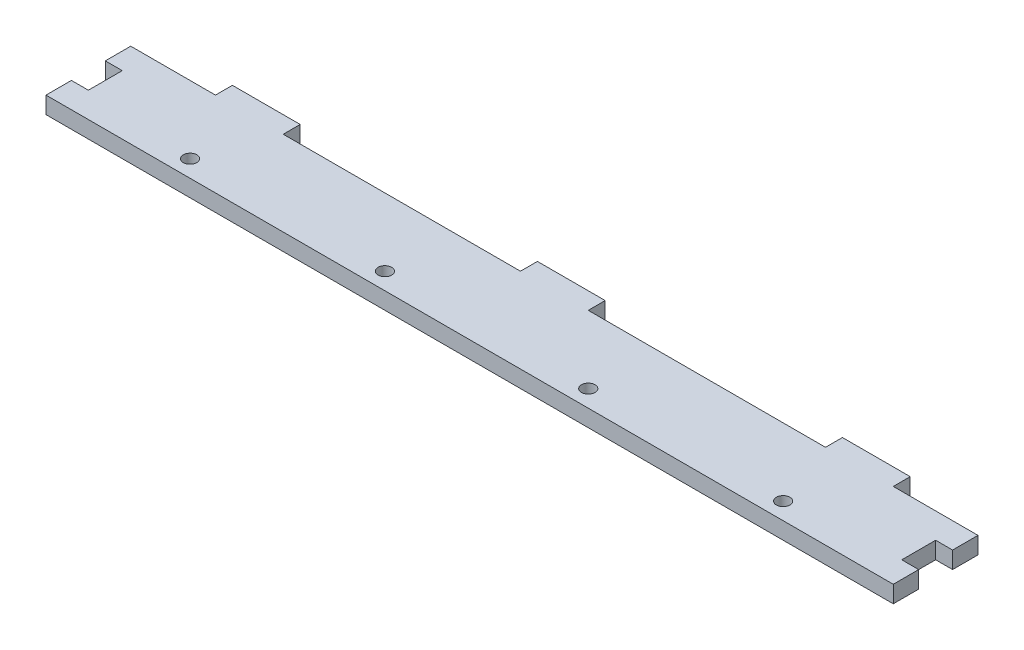
SolidWorks part; units mm, degrees
material "Very Low Density PE (SS)"
ref_plane "Front Plane" through (0, 0, 0) normal (0, 0, 1) x (1, 0, 0)
ref_plane "Top Plane" through (0, 0, 0) normal (0, 1, 0) x (1, 0, 0)
ref_plane "Right Plane" through (0, 0, 0) normal (1, 0, 0) x (0, 0, -1)
sketch "Sketch1" plane through (0, 0, 0) normal (0, 1, 0) x (1, 0, 0)
  line L0 (0, -12.5) -> (0, 15) construction
  line L1 (-125, 12.5) -> (-100, 12.5)
  line L2 (-125, 12.5) -> (-125, 5)
  line L3 (-125, -12.5) -> (125, -12.5)
  line L4 (125, 12.5) -> (125, 5)
  line L5 (-125, 12.5) -> (125, -12.5) construction
  line L6 (-125, -12.5) -> (125, 12.5) construction
  line L7 (100, 17.5) -> (80, 17.5)
  line L9 (-100, 12.5) -> (-100, 17.5)
  line L10 (-100, 17.5) -> (-80, 17.5)
  line L11 (-80, 12.5) -> (-80, 17.5)
  line L12 (80, 12.5) -> (80, 17.5)
  line L14 (100, 12.5) -> (100, 17.5)
  line L15 (-80, 12.5) -> (-10, 12.5)
  line L16 (100, 12.5) -> (125, 12.5)
  line L17 (10, 12.5) -> (80, 12.5)
  line L18 (-10, 17.5) -> (10, 17.5)
  line L19 (-10, 17.5) -> (-10, 12.5)
  line L21 (10, 17.5) -> (10, 12.5)
  line L22 (-10, 17.5) -> (10, 12.5) construction
  line L23 (-10, 12.5) -> (10, 17.5) construction
  line L24 (-125, -7.5) -> (125, -7.5) construction
  line L25 (120, 5) -> (125, 5)
  line L26 (-120, -5) -> (-125, -5)
  line L27 (-120, -5) -> (-120, 5)
  line L28 (-120, 5) -> (-125, 5)
  line L29 (-125, -5) -> (-125, 5) construction
  line L30 (-120, -5) -> (-125, 5) construction
  line L31 (-120, 5) -> (-125, -5) construction
  line L32 (125, -5) -> (125, 5) construction
  line L33 (120, -5) -> (125, -5)
  line L34 (120, -5) -> (120, 5)
  line L35 (-125, 5) -> (-125, -5) construction
  line L36 (-125, -5) -> (-125, -12.5)
  line L37 (125, 5) -> (125, -5) construction
  line L38 (125, -5) -> (125, -12.5)
  circle A0 centre (-30, -7.5) radius 2
  circle A1 centre (-87.5, -7.5) radius 2
  circle A2 centre (30, -7.5) radius 2
  circle A3 centre (87.5, -7.5) radius 2
  point P0 (0, 0)
  point P18 (0, 15)
  point P31 (-122.5, 0)
  dimension "D8" = 4
  dimension "D10" = 4
  dimension "D12" = 10
  dimension "D1" = 250
  dimension "D2" = 25
  dimension "D3" = 20
  dimension "D4" = 5
  dimension "D5" = 25
  dimension "D6" = 20
  dimension "D7" = 5
  dimension "D9" = 30
  dimension "D11" = 87.5
  dimension "D13" = 5
extrude "Boss-Extrude1" add sketch "Sketch1" along normal blind 5
